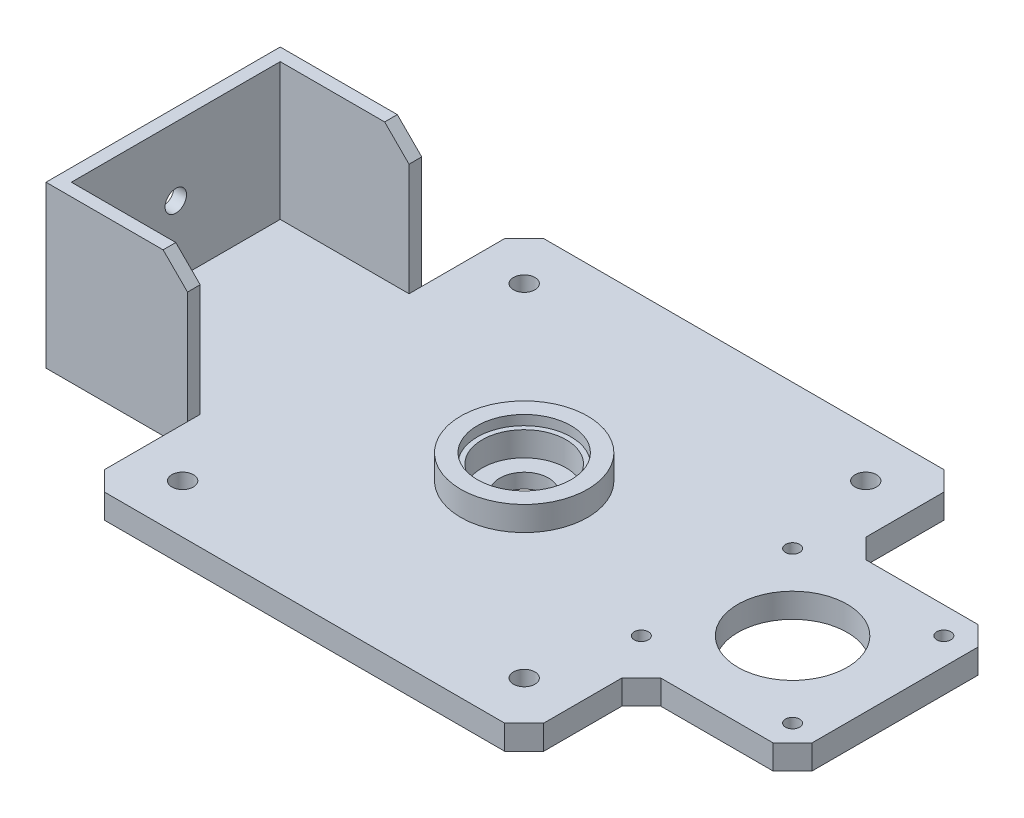
SolidWorks part; units mm, degrees
ref_plane "Front Plane" through (0, 0, 0) normal (0, 0, 1) x (1, 0, 0)
ref_plane "Top Plane" through (0, 0, 0) normal (0, 1, 0) x (1, 0, 0)
ref_plane "Right Plane" through (0, 0, 0) normal (1, 0, 0) x (0, 0, -1)
sketch "Sketch1" plane through (0, 0, 0) normal (0, 1, 0) x (1, 0, 0)
  line L0 (-134.1176, 0) -> (172.5028, 0) construction
  line L1 (-45, 45) -> (45, 45)
  line L2 (45, 45) -> (45, 21)
  line L3 (45, 21) -> (76, 21)
  line L4 (76, 21) -> (76, -21)
  line L5 (-45, 45) -> (-45, 24)
  line L6 (-45, 24) -> (-74, 24)
  line L7 (-74, 24) -> (-74, -24)
  line L8 (-45, 24) -> (-45, 21.4)
  line L9 (-45, 21.4) -> (-71.4, 21.4)
  line L10 (-71.4, 21.4) -> (-71.4, -21.4)
  line L11 (-45, -21.4) -> (-71.4, -21.4)
  line L12 (-45, -24) -> (-45, -21.4)
  line L13 (-45, -24) -> (-74, -24)
  line L14 (-45, -45) -> (-45, -24)
  line L15 (45, -21) -> (76, -21)
  line L16 (45, -45) -> (45, -21)
  line L17 (-45, -45) -> (45, -45)
  line L18 (0, 88.6779) -> (0, -78.3548) construction
  circle A0 centre (70.5, 15.5) radius 1.45
  circle A1 centre (39.5, 15.5) radius 1.45
  circle A2 centre (35, 35) radius 2.2
  circle A3 centre (-35, 35) radius 2.2
  circle A4 centre (-35, -35) radius 2.2
  circle A5 centre (35, -35) radius 2.2
  circle A6 centre (39.5, -15.5) radius 1.45
  circle A7 centre (70.5, -15.5) radius 1.45
  circle A8 centre (0, 0) radius 5
  circle A9 centre (0, 0) radius 8.6
  circle A10 centre (0, 0) radius 9.6
  circle A11 centre (0, 0) radius 13
  circle A12 centre (55, 0) radius 11.2
  dimension "D6" = 4.4
  dimension "D7" = 10
  dimension "D8" = 17.2
  dimension "D9" = 19.2
  dimension "D10" = 26
  dimension "D14" = 2.9
  dimension "D16" = 2.9
  dimension "D17" = 22.4
  dimension "D1" = 90
  dimension "D2" = 42
  dimension "D3" = 90
  dimension "D4" = 10
  dimension "D5" = 10
  dimension "D11" = 31
  dimension "D12" = 5.5
  dimension "D13" = 5.5
  dimension "D15" = 31
  dimension "D18" = 21
  dimension "D19" = 29
  dimension "D20" = 26.4
  dimension "D21" = 48
  dimension "D22" = 42.8
extrude "Boss-Extrude1" add sketch "Sketch1" along normal blind 5 contours L14 L17 L16 L15 L4 L3 L2 L1 L5 L8 L9 L10 L11 L12 A12 A11 A6 A4 A3 A2 A1 A0 A5 A7 | L13 L12 L11 L10 L9 L8 L6 L7 region at (0, 0, -43.273) region at (-45.5608, 0, -22.7)
extrude "Boss-Extrude2" add sketch "Sketch1<3>" along normal blind 33 contours L13 L12 L11 L10 L9 L8 L6 L7 region at (-45.5608, 0, -22.7)
sketch "Sketch1<3>" plane through (0, 0, 0) normal (0, 1, 0) x (1, 0, 0) same geometry as "Sketch1"
extrude "Boss-Extrude3" add sketch "Sketch1<4>" along normal blind 3 contours A11 A10 | A10 A9 | A9 A8 region at (-8.3568, 0, 0) region at (-9.3285, 0, 0) region at (-12.6323, 0, 0)
sketch "Sketch1<4>" plane through (0, 0, 0) normal (0, 1, 0) x (1, 0, 0) same geometry as "Sketch1"
extrude "Boss-Extrude4" add sketch "Sketch1<5>" along normal blind 8 contours A10 A9 | A11 A10 region at (-9.3285, 0, 0) region at (-12.6323, 0, 0)
sketch "Sketch1<5>" plane through (0, 0, 0) normal (0, 1, 0) x (1, 0, 0) same geometry as "Sketch1"
extrude "Boss-Extrude5" add sketch "Sketch1<6>" along normal blind 10 contours A11 A10 region at (-12.6323, 0, 0)
sketch "Sketch1<6>" plane through (0, 0, 0) normal (0, 1, 0) x (1, 0, 0) same geometry as "Sketch1"
sketch "Sketch2" plane through (-71.4, 0, 0) normal (1, 0, 0) x (0, 0, -1)
  line L0 (0, -15.4248) -> (0, 46.2397) construction
  line L1 (21.4, 33) -> (-21.4, 33) construction
  circle A0 centre (0, 19) radius 2.2
  dimension "D2" = 4.4
  dimension "D1" = 14
extrude "Cut-Extrude1" cut sketch "Sketch2" against normal blind 10
chamfer "Chamfer1" distance 4 8 edges at (-45, 2.5, 45) (-45, 2.5, -45) (45, 2.5, -45) (45, 2.5, -21) (76, 2.5, -21) (76, 2.5, 21) (45, 2.5, 21) (45, 2.5, 45)
chamfer "Chamfer2" distance 5 2 edges at (-45, 33, -22.7) (-45, 33, 22.7)
